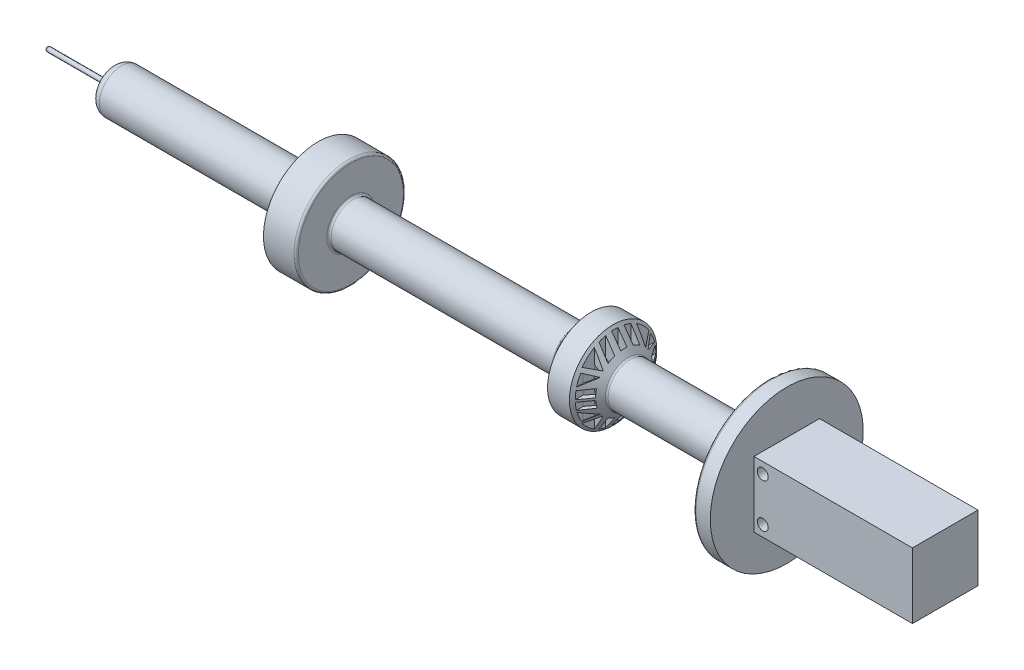
SolidWorks part; units mm, degrees
material "1060 Alloy"
ref_plane "Front Plane" through (0, 0, 0) normal (0, 0, 1) x (1, 0, 0)
ref_plane "Top Plane" through (0, 0, 0) normal (0, 1, 0) x (1, 0, 0)
ref_plane "Right Plane" through (0, 0, 0) normal (1, 0, 0) x (0, 0, -1)
sketch "Sketch1" plane through (0, 0, 0) normal (0, 1, 0) x (1, 0, 0)
  line L0 (-569.1703, 0) -> (569.1703, 0) construction
  line L1 (-569.1703, 0) -> (-569.1703, 25.4)
  line L2 (-569.1703, 25.4) -> (-330.2, 25.4)
  line L3 (-330.2, 25.4) -> (-330.2, 0)
  line L4 (-330.2, 25.4) -> (-330.2, 63.5)
  line L5 (-330.2, 63.5) -> (-292.1, 63.5)
  line L6 (-292.1, 63.5) -> (-292.1, 0)
  line L7 (-292.1, 25.4) -> (-31.0314, 25.4)
  line L8 (-31.0314, 25.4) -> (-31.0314, 0)
  line L9 (-12.7, 0) -> (-12.7, 50.8)
  line L10 (-12.7, 50.8) -> (12.7, 50.8)
  line L11 (12.7, 50.8) -> (12.7, 0)
  line L12 (-31.0314, 25.4) -> (-12.7, 50.8)
  line L13 (12.7, 50.8) -> (31.0314, 25.4)
  line L14 (31.0314, 25.4) -> (31.0314, 0)
  line L15 (31.0314, 25.4) -> (183.4314, 25.4)
  line L16 (183.4314, 25.4) -> (183.4314, 0)
  line L17 (183.4314, 61.8025) -> (195.4338, 61.8025)
  line L18 (195.4338, 61.8025) -> (195.4338, 0)
  line L19 (183.4314, 61.8025) -> (183.4314, 25.4)
  line L20 (195.4338, 61.8025) -> (195.4338, 88.9)
  line L21 (195.4338, 88.9) -> (214.5429, 88.9)
  line L22 (214.5429, 88.9) -> (214.5429, 0)
  dimension "D2" = 25.4
  dimension "D4" = 38.1
  dimension "D5" = 38.1
  dimension "D6" = 12.7
  dimension "D7" = 25.4
  dimension "D8" = 88.9
  dimension "D9" = 152.4
  dimension "D10" = 261.0686
revolve "Revolve1" add sketch "Sketch1" angle 360 about L0 region at (-449.6852, 0, -12.7) region at (-311.15, 0, -31.75) region at (-161.5657, 0, -12.7) region at (-20.8473, 0, -19.7556) region at (0, 0, -25.4) region at (20.8473, 0, -19.7556) region at (107.2314, 0, -12.7) region at (189.4326, 0, -30.9013) region at (204.9884, 0, -44.45)
sketch "Sketch2" plane through (214.5429, 0, 0) normal (1, 0, 0) x (0, 0, -1)
  line L1 (-38.1, -38.1) -> (38.1, -38.1)
  line L2 (-38.1, -38.1) -> (-38.1, 38.1)
  line L3 (-38.1, 38.1) -> (38.1, 38.1)
  line L4 (38.1, -38.1) -> (38.1, 38.1)
  line L5 (-38.1, -38.1) -> (38.1, 38.1) construction
  line L6 (-38.1, 38.1) -> (38.1, -38.1) construction
  point P0 (0, 0)
  dimension "D1" = 76.2
  dimension "D2" = 76.2
extrude "Boss-Extrude2" add sketch "Sketch2" along normal blind 177.8
sketch "Sketch5" plane through (392.3429, 0, 0) normal (1, 0, 0) x (0, 0, -1)
  line L1 (-38.1, -38.1) -> (38.1, -38.1)
  line L2 (-38.1, -38.1) -> (-38.1, 38.1)
  line L3 (-38.1, 38.1) -> (38.1, 38.1)
  line L4 (38.1, -38.1) -> (38.1, 38.1)
  line L5 (-38.1, -38.1) -> (38.1, 38.1) construction
  line L6 (-38.1, 38.1) -> (38.1, -38.1) construction
  point P0 (0, 0)
extrude "Boss-Extrude3" add sketch "Sketch5" along normal blind 6.35
fillet "Fillet1" radius 10.16 1 edges at (-569.1703, 0, 25.4)
fillet "Fillet2" radius 2.54 1 edges at (-292.1, 0, 25.4)
fillet "Fillet3" radius 2.54 1 edges at (-330.2, 0, 25.4)
fillet "Fillet4" radius 2.54 1 edges at (-31.0314, 0, 25.4)
fillet "Fillet5" radius 2.54 1 edges at (31.0314, 0, 25.4)
fillet "Fillet6" radius 2.54 1 edges at (183.4314, 0, 25.4)
fillet "Fillet7" radius 2.54 1 edges at (183.4314, 0, 61.8025)
fillet "Fillet8" radius 2.54 1 edges at (195.4338, 0, 61.8025)
fillet "Fillet9" radius 2.54 1 edges at (195.4338, 0, 88.9)
sketch "Sketch6" plane through (-569.1703, 0, 0) normal (-1, 0, 0) x (0, 0, 1)
  circle A0 centre (0, 0) radius 2.54
  dimension "D1" = 5.08
extrude "Boss-Extrude4" add sketch "Sketch6" along normal blind 76.2
fillet "Fillet10" radius 2.54 1 edges at (-645.3703, 0, 2.54)
sketch "Sketch7" plane through (-330.2, 0, 0) normal (-1, 0, 0) x (0, 0, 1)
  circle A0 centre (0, 0) radius 60.1789
  circle A1 centre (0, 0) radius 57.9976
extrude "Cut-Extrude7" cut sketch "Sketch7" against normal blind 2.54
ref_plane "Plane2" through (0, 53.34, 0) normal (0, 1, 0) x (1, 0, 0)
sketch "Sketch10" plane through (0, 53.34, 0) normal (0, 1, 0) x (1, 0, 0)
  line L0 (-25.4989, 25.0554) -> (-15.0079, 39.2932)
  line L1 (-15.0079, 39.2932) -> (-15.0079, 25.0554)
  line L2 (-15.0079, 25.0554) -> (-25.4989, 25.0554)
  line L3 (-25.4989, -24.2148) -> (-15.0079, -24.2148)
  line L4 (-15.0079, -24.2148) -> (-15.0079, -38.4526)
  line L5 (-15.0079, -38.4526) -> (-25.4989, -24.2148)
  line L6 (-25.4989, 18.3112) -> (-15.0079, 18.3112)
  line L7 (-15.0079, 18.3112) -> (-15.0079, 10.4429)
  line L8 (-15.0079, 10.4429) -> (-25.4989, 10.4429)
  line L9 (-25.4989, 10.4429) -> (-25.4989, 18.3112)
  line L10 (-25.4989, -18.782) -> (-15.0079, -18.782)
  line L11 (-15.0079, -18.782) -> (-15.0079, -10.9137)
  line L12 (-15.0079, -10.9137) -> (-25.4989, -10.9137)
  line L13 (-25.4989, -10.9137) -> (-25.4989, -18.782)
  line L14 (-25.4989, 3.324) -> (-15.0079, 3.324)
  line L15 (-15.0079, 3.324) -> (-15.0079, -3.9822)
  line L16 (-15.0079, -3.9822) -> (-25.4989, -3.9822)
  line L17 (-25.4989, -3.9822) -> (-25.4989, 3.324)
  line L18 (0, 50.8) -> (0, -50.8) construction
  line L19 (12.7, 50.8) -> (-12.7, 50.8) construction
  line L20 (-12.7, -50.8) -> (12.7, -50.8) construction
  line L21 (15.0079, -38.4526) -> (25.4989, -24.2148)
  line L22 (15.0079, -24.2148) -> (15.0079, -38.4526)
  line L23 (25.4989, -24.2148) -> (15.0079, -24.2148)
  line L24 (25.4989, -18.782) -> (15.0079, -18.782)
  line L25 (25.4989, -10.9137) -> (25.4989, -18.782)
  line L26 (15.0079, -18.782) -> (15.0079, -10.9137)
  line L27 (15.0079, -10.9137) -> (25.4989, -10.9137)
  line L28 (25.4989, -3.9822) -> (25.4989, 3.324)
  line L29 (15.0079, -3.9822) -> (25.4989, -3.9822)
  line L30 (25.4989, 3.324) -> (15.0079, 3.324)
  line L31 (15.0079, 3.324) -> (15.0079, -3.9822)
  line L32 (15.0079, 10.4429) -> (25.4989, 10.4429)
  line L33 (25.4989, 10.4429) -> (25.4989, 18.3112)
  line L34 (15.0079, 18.3112) -> (15.0079, 10.4429)
  line L35 (25.4989, 18.3112) -> (15.0079, 18.3112)
  line L36 (15.0079, 25.0554) -> (25.4989, 25.0554)
  line L37 (15.0079, 39.2932) -> (15.0079, 25.0554)
  line L38 (25.4989, 25.0554) -> (15.0079, 39.2932)
extrude "Cut-Extrude11" cut sketch "Sketch10" against normal through all
ref_plane "Plane3" through (0, 0, 53.34) normal (0, 0, 1) x (1, 0, 0)
sketch "Sketch11" plane through (0, 0, 53.34) normal (0, 0, 1) x (1, 0, 0)
  line L0 (-25.4724, 17.9592) -> (-15.5521, 23.6035)
  line L1 (-15.5521, 23.6035) -> (-15.5521, 12.0634)
  line L2 (-15.5521, 12.0634) -> (-25.4724, 17.9592)
  line L3 (-25.4724, 8.723) -> (-15.5521, 8.723)
  line L4 (-15.5521, 8.723) -> (-15.5521, 0)
  line L5 (-15.5521, 0) -> (-25.4724, 0)
  line L6 (-25.4724, 0) -> (-25.4724, 8.723)
  line L7 (-15.5521, -2.5658) -> (-15.5521, -11.2888)
  line L8 (-15.5521, -11.2888) -> (-25.4724, -11.2888)
  line L9 (-25.4724, -11.2888) -> (-25.4724, -2.5658)
  line L10 (-25.4724, -2.5658) -> (-15.5521, -2.5658)
  line L11 (-25.4724, -19.3277) -> (-15.5521, -25.2234)
  line L12 (-15.5521, -25.2234) -> (-15.5521, -13.6834)
  line L13 (-15.5521, -13.6834) -> (-25.4724, -19.3277)
  line L14 (0, 50.8) -> (0, -50.8) construction
  line L15 (12.7, 50.8) -> (-12.7, 50.8) construction
  line L16 (-12.7, -50.8) -> (12.7, -50.8) construction
  line L17 (25.4724, -19.3277) -> (15.5521, -25.2234)
  line L18 (15.5521, -25.2234) -> (15.5521, -13.6834)
  line L19 (15.5521, -13.6834) -> (25.4724, -19.3277)
  line L20 (15.5521, -11.2888) -> (25.4724, -11.2888)
  line L21 (15.5521, -2.5658) -> (15.5521, -11.2888)
  line L22 (25.4724, -11.2888) -> (25.4724, -2.5658)
  line L23 (25.4724, -2.5658) -> (15.5521, -2.5658)
  line L24 (15.5521, 0) -> (25.4724, 0)
  line L25 (25.4724, 0) -> (25.4724, 8.723)
  line L26 (15.5521, 8.723) -> (15.5521, 0)
  line L27 (25.4724, 8.723) -> (15.5521, 8.723)
  line L28 (15.5521, 23.6035) -> (15.5521, 12.0634)
  line L29 (15.5521, 12.0634) -> (25.4724, 17.9592)
  line L30 (25.4724, 17.9592) -> (15.5521, 23.6035)
extrude "Cut-Extrude12" cut sketch "Sketch11" against normal through all
fillet "Fillet11" radius 2.54 1 edges at (-292.1, 0, 63.5)
sketch "Sketch12" plane through (0, 0, -38.1) normal (0, 0, -1) x (-1, 0, 0)
  line L0 (-398.6929, 38.1) -> (-214.5429, 38.1) construction
  line L1 (-389.8029, -25.4) -> (-224.7029, -25.4)
  line L2 (-389.8029, -25.4) -> (-389.8029, 25.4)
  line L3 (-389.8029, 25.4) -> (-224.7029, 25.4)
  line L4 (-224.7029, -25.4) -> (-224.7029, 25.4)
  line L5 (-382.1829, 17.78) -> (-232.3229, 17.78)
  line L6 (-214.5429, 88.9) -> (-214.5429, -88.9) construction
  line L11 (-384.7229, 20.32) -> (-229.7829, 20.32)
  line L12 (-229.7829, -20.32) -> (-229.7829, 20.32)
  line L13 (-384.7229, -20.32) -> (-229.7829, -20.32)
  line L14 (-384.7229, -20.32) -> (-384.7229, 20.32)
  line L15 (-232.3229, -17.78) -> (-232.3229, 17.78)
  line L16 (-382.1829, -17.78) -> (-232.3229, -17.78)
  line L17 (-382.1829, -17.78) -> (-382.1829, 17.78)
  circle A0 centre (-389.8029, 25.4) radius 6.35
  circle A1 centre (-389.8029, -25.4) radius 6.35
  circle A2 centre (-224.7029, 25.4) radius 6.35
  circle A3 centre (-224.7029, -25.4) radius 6.35
  dimension "D5" = 12.7
  dimension "D6" = 12.7
  dimension "D7" = 12.7
  dimension "D8" = 12.7
  dimension "D1" = 165.1
  dimension "D2" = 50.8
  dimension "D3" = 12.7
  dimension "D4" = 10.16
  dimension "D11" = 2.54
extrude "Cut-Extrude13" cut sketch "Sketch12" against normal through all contours L4 A2 L3 | L3 A2 L4 | L1 A3 L4 | L4 A3 L1 region at (227.398, -22.705, -38.1) region at (223.8046, -26.2983, -38.1) region at (227.398, 22.705, -38.1) region at (223.8046, 26.2983, -38.1)
extrude "Cut-Extrude14" cut sketch "Sketch12<3>" against normal blind 5.08 contours L14 L13 L12 L11 L16 L17 L5 L15 region at (307.2529, 18.7182, -38.1)
sketch "Sketch12<3>" plane through (0, 0, -38.1) normal (0, 0, -1) x (-1, 0, 0) same geometry as "Sketch12"
